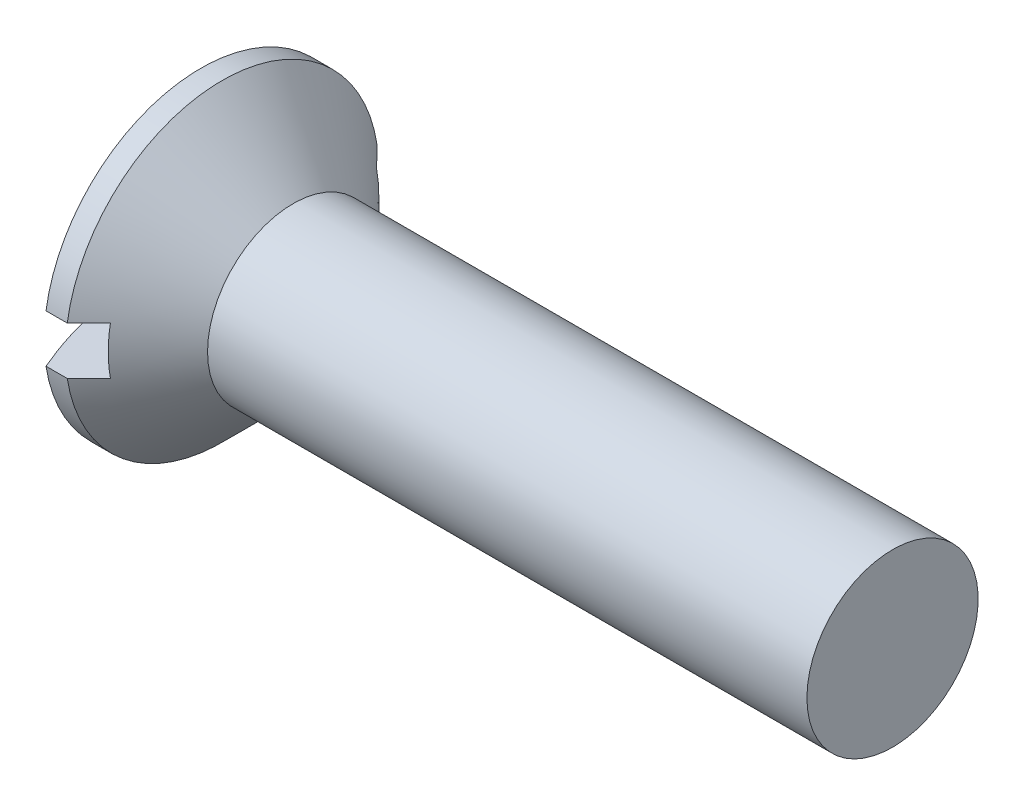
SolidWorks part; units mm, degrees
revolve "Base-Revolve" add sketch "BodySke" angle 360 about L4 other way angle 60
sketch "BodySke" plane through (0, 0, 0) normal (0, 0, 1) x (1, 0, 0)
  line L0 (0, 0) -> (42.2988, 0)
  line L1 (42.2988, 0) -> (42.2988, 5)
  line L2 (42.2988, 5) -> (7.2988, 5)
  line L3 (7.2988, 5) -> (-0.5742, 12.873) construction
  line L4 (-15.875, 0) -> (82.55, 0) construction
  line L5 (7.2988, -5) -> (-0.5742, -12.873) construction
  line L6 (8.7988, 8.175) -> (8.7988, -7.7) construction
  line L7 (2.2988, 5.2375) -> (2.2988, -10.6375) construction
  line L8 (7.2988, 5) -> (3.1488, 9.15)
  line L9 (3.1488, 9.15) -> (1.9074, 9.15)
  arc A0 (0, 0) -> (1.9074, 9.15) centre (22.9, 0) cw
  arc A1 (2.2988, 10) -> (0, 0) centre (22.9, 0) ccw construction
  dimension "Diameter" = 10
  dimension "Head_ang" = 90
  dimension "D3" = 20
  dimension "D4" = 2.2988
  dimension "Length" = 40
  dimension "Head_dia" = 18.3
cosmetic thread "ThreadCosmetic" [suppressed] parameters "Thread_length"=33.5, "Thread_minor"=8.344
ref_plane "Plane1" through (0, 0, 0) normal (0, 0, 1) x (1, 0, 0)
ref_plane "Plane2" through (0, 0, 0) normal (0, 1, 0) x (1, 0, 0)
ref_plane "Plane3" through (0, 0, 0) normal (1, 0, 0) x (0, 0, -1)
sketch "Sketch2" plane through (0, 0, 0) normal (1, 0, 0) x (0, 0, -1)
  line L0 (9.15, -1.4) -> (-9.15, -1.4)
  line L1 (9.15, -1.4) -> (9.15, 1.4)
  line L2 (-9.15, 1.4) -> (9.15, 1.4)
  line L3 (-9.15, 1.4) -> (-9.15, -1.4)
  dimension "D1" = 18.3
  dimension "D3" = 9.15
  dimension "D4" = 1.4
extrude "Slot" cut sketch "Sketch2" along normal blind 4.4
sketch "Sketch3" plane through (0, 0, 0) normal (1, 0, 0) x (0, 0, -1)
  line L0 (1.085, -5.62) -> (-1.085, -5.62)
  line L1 (1.085, -5.62) -> (1.085, 5.62)
  line L2 (-1.085, 5.62) -> (1.085, 5.62)
  line L3 (-1.085, 5.62) -> (-1.085, -5.62)
  dimension "D1" = 1.085
  dimension "D2" = 5.62
ref_plane "Plane4" through (7.15, 0, 0) normal (1, 0, 0) x (0, 0, -1)
sketch "Sketch4" plane through (7.15, 0, 0) normal (1, 0, 0) x (0, 0, -1)
  line L0 (0.5425, -0.5425) -> (-0.5425, -0.5425)
  line L1 (0.5425, -0.5425) -> (0.5425, 0.5425)
  line L2 (-0.5425, 0.5425) -> (0.5425, 0.5425)
  line L3 (-0.5425, 0.5425) -> (-0.5425, -0.5425)
  dimension "D1" = 1.085
  dimension "D2" = 1.085
  dimension "D3" = 0.5425
  dimension "D4" = 0.5425
loft "Cross" cut profiles "Sketch3", "Sketch4"
pattern_circular "CirPattern1" count 2 every 90 about axis through (-15.875, 0, 0) along (1, 0, 0) of "Cross"
sketch "ThdSchSke" plane through (0, 0, 0) normal (0, 0, 1) x (1, 0, 0)
  line L0 (8.7988, -4.172) -> (8.219, -5)
  line L1 (8.7988, -4.172) -> (9.3786, -5)
  line L2 (9.3786, -5) -> (9.3786, -6.25)
  line L3 (-3.175, 0) -> (5.1513, 0) construction
  line L5 (9.3786, -6.25) -> (8.219, -6.25)
  line L6 (8.219, -6.25) -> (8.219, -5)
  line L8 (42.2988, -5) -> (42.2988, 5) construction
  dimension "Diameter" = 10
  dimension "Thread_minor" = 8.344
  dimension "Start" = 33.5
revolve "ThreadSchematic" [suppressed] cut sketch "ThdSchSke" angle 360 about L3
pattern_linear "ThdSchPat" [suppressed]
equation "\"D1@Sketch2\" = \"Head_dia@BodySke\""
equation "\"D3@Sketch2\" = \"D1@Sketch2\" / 2"
equation "\"D4@Sketch2\" = \"Slot_width@Sketch2\" / 2"
equation "\"D1@Sketch3\" = \"Cross_width@Sketch3\" / 2"
equation "\"D2@Sketch3\" = \"Cross_dia@Sketch3\" / 2"
equation "\"D1@Sketch4\" = \"Cross_width@Sketch3\"*.5"
equation "\"D2@Sketch4\" = \"D1@Sketch4\""
equation "\"D3@Sketch4\" = \"D1@Sketch4\" / 2"
equation "\"D4@Sketch4\" = \"D2@Sketch4\" / 2"
equation "\"Thread_length@ThreadCosmetic\" = ((sgn( (\"Length@BodySke\" - \"Advance@BodySke\" - \"Side_ht@BodySke\" ) - \"Thread_nom@BodySke\" )-1)*( (\"Length@BodySke\" - \"Advance@BodySke\" - \"Side_ht@BodySke\" ) - \"Thread_nom@BodySke\" ))/-2+ \"Thread_nom@BodySke\""
equation "\"Thread_minor@ThdSchSke\" = \"Thread_minor@ThreadCosmetic\""
equation "\"Diameter@ThdSchSke\" = \"Diameter@BodySke\""
equation "\"Overcut@ThdSchSke\" = \"Diameter@BodySke\" * 1.25"
equation "\"Start@ThdSchSke\" =  \"Thread_length@ThreadCosmetic\""
equation "\"Num_threads@ThdSchPat\" = int( \"Thread_length@ThreadCosmetic\" / \"Advance@BodySke\" + 0.999 )  + 1"
equation "\"Advance@ThdSchPat\" = \"Thread_length@ThreadCosmetic\" /  (\"Num_threads@ThdSchPat\" - 1) 'relax it"
